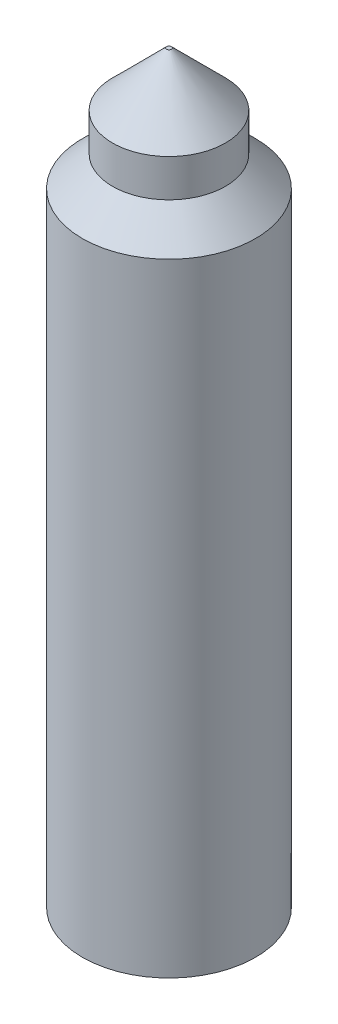
SolidWorks part; units mm, degrees
ref_plane "Front Plane" through (0, 0, 0) normal (0, 0, 1) x (1, 0, 0)
ref_plane "Top Plane" through (0, 0, 0) normal (0, 1, 0) x (1, 0, 0)
ref_plane "Right Plane" through (0, 0, 0) normal (1, 0, 0) x (0, 0, -1)
sketch "Sketch1" plane through (0, 0, 0) normal (0, 1, 0) x (1, 0, 0)
  circle A0 centre (0, 0) radius 12.8
extrude "Boss-Extrude1" add sketch "Sketch1" along normal blind 100
sketch "Sketch2" plane through (0, 100, 0) normal (0, 1, 0) x (1, 0, 0)
  circle A0 centre (0, 0) radius 132.202
sketch "Sketch3" plane through (0, 100, 0) normal (0, 1, 0) x (1, 0, 0)
  circle A0 centre (0, 0) radius 8.3488
extrude "Boss-Extrude3" add sketch "Sketch3" along normal blind 10
chamfer "Chamfer3" distance 8 angle 45 1 edges at (0, 110, 8.3488)
chamfer "Chamfer4" distance 8 angle 45 1 edges at (0, 100, 12.8)
